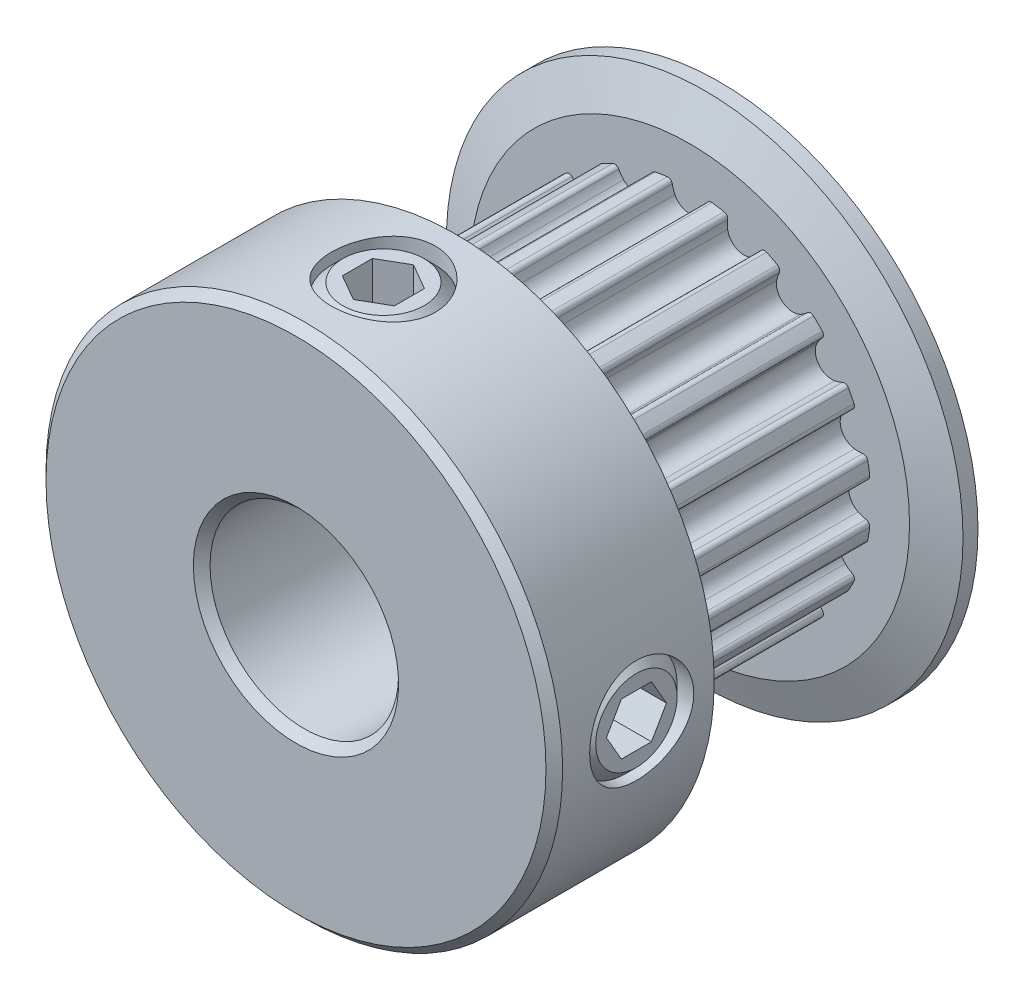
SolidWorks part; units mm, degrees
ref_plane "Front Plane" through (0, 0, 0) normal (0, 0, 1) x (1, 0, 0)
ref_plane "Top Plane" through (0, 0, 0) normal (0, 1, 0) x (1, 0, 0)
ref_plane "Right Plane" through (0, 0, 0) normal (1, 0, 0) x (0, 0, -1)
sketch "Sketch1" plane through (0, 0, 0) normal (0, 0, 1) x (1, 0, 0)
  line L1 (-1.7499, 5.3585) -> (1.7499, 5.3585) construction
  line L4 (0, 0) -> (0, 5.3585) construction
  line L5 (0, 5.3585) -> (0, 11.211) construction
  line L6 (0, 6.3625) -> (1.9751, 6.0482) construction
  line L7 (1.9751, 6.0482) -> (2.6648, 5.8229) construction
  line L8 (1.9751, 6.0482) -> (1.7499, 5.3585) construction
  line L9 (-1.9751, 6.0482) -> (-1.7499, 5.3585) construction
  line L10 (-1.8963, 5.8067) -> (-2.841, 8.6995)
  line L11 (-2.841, 8.6995) -> (2.841, 8.6995)
  line L12 (2.841, 8.6995) -> (1.8963, 5.8067)
  circle A0 centre (0, 0) radius 6.3625 construction
  circle A1 centre (0, 0) radius 8.6995 construction
  circle A2 centre (0, 0) radius 6.1085 construction
  arc A3 (-0.4989, 5.6703) -> (0.4989, 5.6703) centre (0, 5.9135) ccw
  arc A4 (-0.4989, 5.6703) -> (-0.5855, 5.9387) centre (0.4, 6.1085) cw
  arc A5 (-1.8963, 5.8067) -> (-0.7518, 6.0621) centre (0, 0) cw
  arc A6 (-0.5855, 5.9387) -> (-0.7518, 6.0621) centre (-0.7333, 5.9132) ccw
  arc A7 (1.8963, 5.8067) -> (0.7518, 6.0621) centre (0, 0) ccw
  arc A8 (0.5855, 5.9387) -> (0.7518, 6.0621) centre (0.7333, 5.9132) cw
  arc A9 (0.4989, 5.6703) -> (0.5855, 5.9387) centre (-0.4, 6.1085) ccw
  point P6 (0, 20.9083)
  point P11 (0, 6.3625)
  point P13 (0, 8.6995)
  point P14 (0, 6.1085)
  dimension "D1" = 9.6973
  dimension "D2" = 4.8485
sketch "Sketch2" plane through (0, 0, 0) normal (1, 0, 0) x (0, 0, -1)
  line L0 (-7.135, 3.175) -> (7.135, 3.175)
  line L1 (-7.135, 3.175) -> (-7.135, 8.6995)
  line L2 (-1.75, 8.6995) -> (-7.135, 8.6995)
  line L3 (-2.255, 3.175) -> (-2.255, 8.6995) construction
  line L4 (-2.255, 8.6995) -> (-1.245, 8.6995) construction
  line L5 (-1.245, 8.6995) -> (-1.245, 6.1085) construction
  line L6 (-1.245, 6.1085) -> (6.125, 6.1085)
  line L7 (6.125, 6.1085) -> (6.125, 8.6995) construction
  line L8 (6.125, 8.6995) -> (7.135, 8.6995) construction
  line L9 (7.135, 8.6995) -> (7.135, 3.175)
  line L10 (-7.135, 0) -> (7.135, 0) construction
  line L11 (6.63, 8.6995) -> (6.125, 7.404)
  line L12 (-1.245, 7.404) -> (-1.75, 8.6995)
  line L14 (-1.245, 7.404) -> (-1.245, 6.1085)
  line L15 (6.125, 6.1085) -> (6.125, 7.404)
  line L16 (6.63, 8.6995) -> (7.135, 8.6995)
  arc A0 (-1.245, 7.404) -> (-1.75, 8.6995) centre (-3.1592, 7.404) ccw construction
  arc A1 (6.125, 7.404) -> (6.63, 8.6995) centre (8.0392, 7.404) cw construction
  point P12 (-1.245, 7.404)
  point P14 (-1.75, 8.6995)
  point P20 (6.125, 7.404)
  point P21 (6.63, 8.6995)
  point P25 (6.125, 0)
  point P26 (-1.245, 0)
  dimension "OA" = 14.27
  dimension "Bore" = 6.35
  dimension "Outside Width" = 8.38
  dimension "Inside Width" = 7.37
revolve "Revolve1" add sketch "Sketch2" angle 360 mid plane about L10
sketch "Sketch3" plane through (0, 0, 0) normal (0, 0, 1) x (1, 0, 0)
  line L6 (2.841, 8.6995) -> (-2.841, 8.6995)
  line L7 (1.8963, 5.8067) -> (2.841, 8.6995)
  line L8 (-2.841, 8.6995) -> (-1.8963, 5.8067)
  line L9 (2.841, 8.6995) -> (-2.841, 8.6995)
  line L10 (1.8963, 5.8067) -> (2.841, 8.6995)
  line L11 (-2.841, 8.6995) -> (-1.8963, 5.8067)
  arc A8 (1.8963, 5.8067) -> (0.7518, 6.0621) centre (0, 0) ccw
  arc A9 (0.7518, 6.0621) -> (0.5855, 5.9387) centre (0.7333, 5.9132) ccw
  arc A10 (0.4989, 5.6703) -> (0.5855, 5.9387) centre (-0.4, 6.1085) ccw
  arc A11 (-0.4989, 5.6703) -> (0.4989, 5.6703) centre (0, 5.9135) ccw
  arc A12 (-0.5855, 5.9387) -> (-0.4989, 5.6703) centre (0.4, 6.1085) ccw
  arc A13 (-0.5855, 5.9387) -> (-0.7518, 6.0621) centre (-0.7333, 5.9132) ccw
  arc A14 (-0.7518, 6.0621) -> (-1.8963, 5.8067) centre (0, 0) ccw
  arc A15 (1.8963, 5.8067) -> (0.7518, 6.0621) centre (0, 0) ccw
  arc A16 (0.7518, 6.0621) -> (0.5855, 5.9387) centre (0.7333, 5.9132) ccw
  arc A17 (0.4989, 5.6703) -> (0.5855, 5.9387) centre (-0.4, 6.1085) ccw
  arc A18 (-0.4989, 5.6703) -> (0.4989, 5.6703) centre (0, 5.9135) ccw
  arc A19 (-0.5855, 5.9387) -> (-0.4989, 5.6703) centre (0.4, 6.1085) ccw
  arc A20 (-0.5855, 5.9387) -> (-0.7518, 6.0621) centre (-0.7333, 5.9132) ccw
  arc A21 (-0.7518, 6.0621) -> (-1.8963, 5.8067) centre (0, 0) ccw
  dimension "D1" = 0
extrude "Cut-Extrude1" cut sketch "Sketch3" against normal up to vertex (6.125 mm away) from vertex up to point (0, 6.1085, -6.125) starting at point (0, 6.1085, 1.245)
pattern_circular "CirPattern1" count 20 over 360 about axis through (0, 0, 7.135) along (0, 0, 1) of "Cut-Extrude1"
sketch "Sketch4" plane through (0, 0, 0) normal (1, 0, 0) x (0, -1, 0)
  line L0 (0, -1.245) -> (0, -7.135) construction
  line L1 (-3.175, -7.135) -> (3.175, -7.135) construction
  line L2 (7.404, -1.245) -> (-7.404, -1.245) construction
  circle A0 centre (0, -4.19) radius 1.7526
extrude "Cut-Extrude2" cut sketch "Sketch4" along normal through all
ref_plane "Plane1" through (0, 0, 4.19) normal (0, 0, 1) x (1, 0, 0)
sketch "Sketch5" plane through (0, 0, 4.19) normal (0, 0, 1) x (1, 0, 0)
  line L0 (0, 0) -> (0, 8.6995) construction
  line L1 (3.175, -1.3716) -> (3.175, 0)
  line L2 (3.556, -1.7526) -> (8.1401, -1.7526)
  line L3 (3.175, 0) -> (8.6995, 0) construction
  line L4 (3.175, 0) -> (8.5211, 0)
  line L5 (8.5211, 0) -> (8.5211, -1.3716)
  line L6 (3.556, -1.7526) -> (3.175, -1.3716)
  line L7 (8.5211, -1.3716) -> (8.1401, -1.7526)
  circle A0 centre (0, 0) radius 8.6995 construction
  circle A1 centre (0, 0) radius 3.175 construction
  point P2 (3.175, -1.7526)
  point P11 (8.5211, -1.7526)
revolve "Revolve2" add sketch "Sketch5" angle 360 mid plane about L4
sketch "Sketch6" plane through (8.5211, 5.3841, 0) normal (-1, 0, 0) x (0, -1, 0)
  line L1 (5.3841, 5.2019) -> (4.5078, 4.6959)
  line L2 (4.5078, 4.6959) -> (4.5078, 3.6841)
  line L3 (4.5078, 3.6841) -> (5.3841, 3.1781)
  line L4 (5.3841, 3.1781) -> (6.2604, 3.6841)
  line L5 (6.2604, 3.6841) -> (6.2604, 4.6959)
  line L6 (6.2604, 4.6959) -> (5.3841, 5.2019)
  circle A0 centre (5.3841, 4.19) radius 0.8763 construction
  dimension "D1" = 1.7526
extrude "Cut-Extrude3" cut sketch "Sketch6" along normal blind 1.3144
pattern_circular "CirPattern3" count 2 over 90 about axis through (0, 0, 7.135) along (0, 0, 1) of "Cut-Extrude2", "Revolve2", "Cut-Extrude3"
chamfer "Chamfer1" distance 0.2807 angle 45 2 edges at (3.175, 0, 7.135) (8.6995, 0, 7.135)
ref_axis "Center Axis 1" through (0, 0, -7.135) along (0, 0, 1)
ref_plane "Contact Plane 1" through (0, 0, 7.135) normal (0, 0, 1) x (1, 0, 0)
ref_plane "Contact Plane 2" through (0, 0, -7.135) normal (0, 0, -1) x (-1, 0, 0)
equation "\"D2@Sketch1\"= \"D1@Sketch1\" / 2"
equation "\"D1@Sketch6\" = \"Set Screw@Sketch4\" / 2"
equation "\"D1@Cut-Extrude3\" = \"D1@Sketch6\"*.75"
